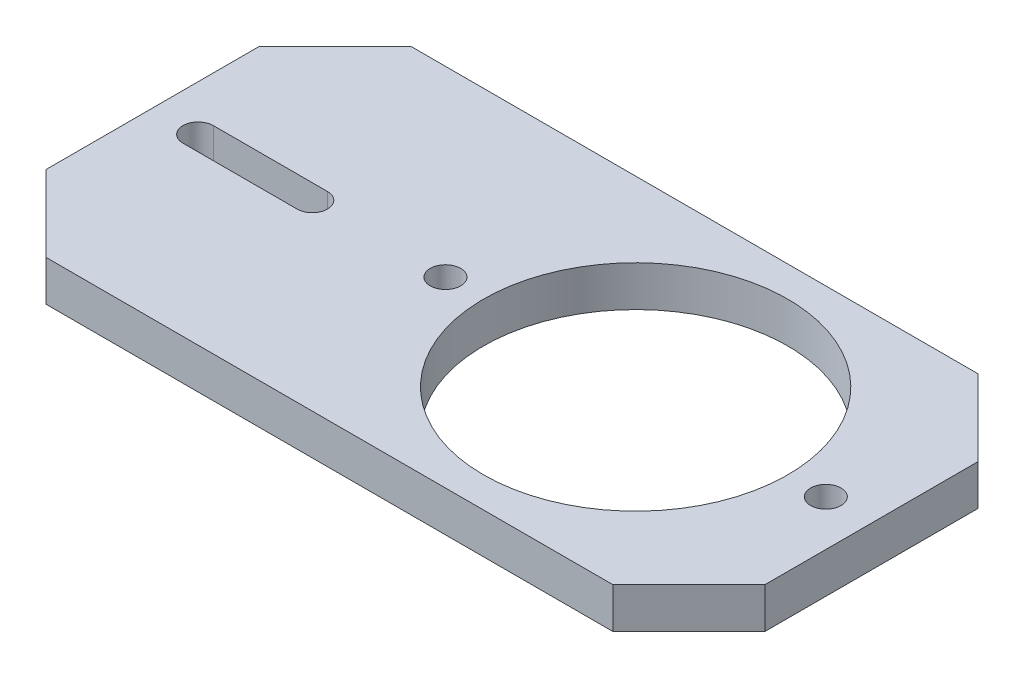
SolidWorks part; units mm, degrees
material "Pine"
ref_plane "Front Plane" through (0, 0, 0) normal (0, 0, 1) x (1, 0, 0)
ref_plane "Top Plane" through (0, 0, 0) normal (0, 1, 0) x (1, 0, 0)
ref_plane "Right Plane" through (0, 0, 0) normal (1, 0, 0) x (0, 0, -1)
sketch "Sketch1" plane through (0, 0, 0) normal (0, 1, 0) x (1, 0, 0)
  line L0 (-57.5, 2) -> (-42.5, 2)
  line L1 (-57.5, -2) -> (-42.5, -2)
  line L2 (-84.5376, 0) -> (67.9764, 0) construction
  line L3 (-50, 2) -> (-50, -2) construction
  line L4 (-63.5, 14) -> (-53.5, 24)
  line L5 (-53.5, 24) -> (21, 24)
  line L6 (-63.5, 14) -> (-63.5, -14)
  line L7 (-53.5, -24) -> (21, -24)
  line L8 (31, 14) -> (31, -14)
  line L9 (-63.5, -14) -> (-53.5, -24)
  line L10 (21, -24) -> (31, -14)
  line L11 (21, 24) -> (31, 14)
  circle A0 centre (-25, 0) radius 2
  circle A1 centre (25, 0) radius 2
  arc A2 (-42.5, -2) -> (-42.5, 2) centre (-42.5, 0) ccw
  arc A4 (-57.5, 2) -> (-57.5, -2) centre (-57.5, 0) ccw
  circle A5 centre (0, 0) radius 20
  point P19 (-63.5, 24)
  point P20 (31, -24)
  point P21 (-63.5, -24)
  point P22 (31, 24)
  dimension "D1" = 4
  dimension "D2" = 4
  dimension "D4" = 4
  dimension "D5" = 75
  dimension "D8" = 4
  dimension "D10" = 40
  dimension "D12" = 6
  dimension "D3" = 50
  dimension "D6" = 15
  dimension "D7" = 6
  dimension "D11" = 25
  dimension "D14" = 24
extrude "Boss-Extrude1" add sketch "Sketch1" against normal blind 5.333
equation "\"rod_diameter\"= 8"
equation "\"rod_hole_thickness\"= 4"
equation "\"rod_radius\"= \"rod_diameter\" / 2"
equation "\"platter_diameter\"= 320"
equation "\"platter_radius\"= \"platter_diameter\" / 2"
equation "\"extruder_mount_hole_spacing\"= 75"
equation "\"arm_rod_spacing\"= 40"
equation "\"motor_level_rod_spacing\"= 15"
equation "\"linear_bearing_diameter\"= 15"
equation "\"z_rod_spacing\"= 75"
equation "\"platter_rod_spacing\"= 50"
equation "\"rod_nut_thickness\"= 6.5"
equation "\"rod_nut_inscribed_diameter\"= 13"
equation "\"z_height\"= 400"
equation "\"gear_pitch\"=2"
equation "\"r_gear_teeth\"= 450"
equation "\"theta_gear_teeth\"= 385"
equation "\"D12@Sketch1\"=2 + \"rod_hole_thickness\""
equation "\"D14@Sketch1\"=\"D10@Sketch1\"/2+\"rod_hole_thickness\""
equation "\"D7@Sketch1\" = \"rod_hole_thickness\" + 2"
equation "\"D5@Sketch1\"=\"extruder_mount_hole_spacing\""
equation "\"top_frame_spacing\"= 100"
equation "\"z_drive_rod_offset\"= 12"
equation "\"sheet_thickness\"=5.333"
equation "\"sheet_tab_hole_thickness\"= \"sheet_thickness\""
equation "\"sheet_tab_width\"= \"sheet_thickness\"*2"
equation "\"sheet_double_tab_width\"= 35"
equation "\"sheet_bolt_diameter\"= 3"
equation "\"sheet_bolt_length\"= 16"
equation "\"sheet_nut_diameter\"= 5.5"
equation "\"sheet_nut_thickness\"= 2.5"
equation "\"sheet_nut_depth\"= 10"
equation "\"bearing_outside_diameter\"= 22"
equation "\"bearing_thickness\"= 7"
equation "\"corner_part_thickness\"= \"sheet_thickness\" + \"bearing_thickness\""
equation "\"setscrew_nut_diameter\"= 6"
equation "\"setscrew_nut_thickness\"= 3"
equation "\"setscrew_bolt_diameter\"= 3"
equation "\"motor_shaft_diameter\"= 5.7"
equation "\"D1@Boss-Extrude1\"= \"sheet_thickness\""
